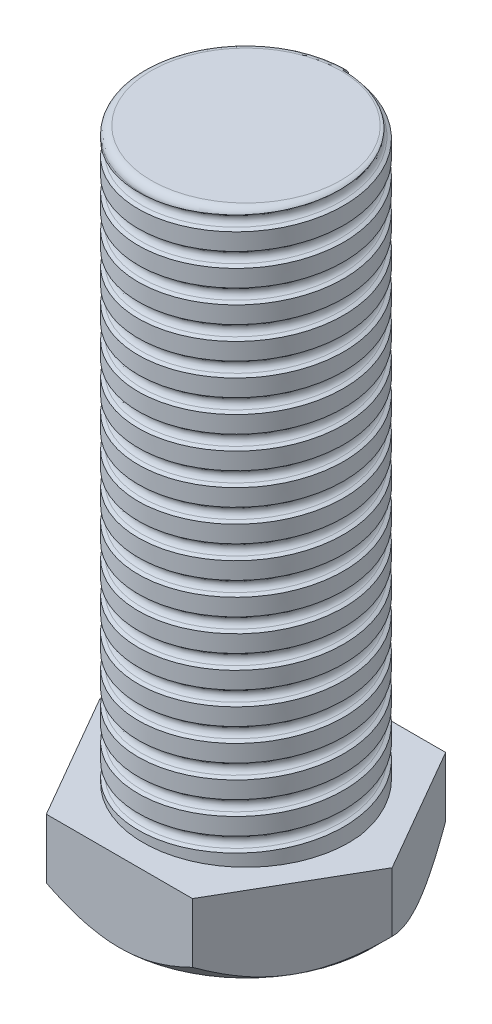
SolidWorks part; units mm, degrees
ref_plane "Front Plane" through (0, 0, 0) normal (0, 0, 1) x (1, 0, 0)
ref_plane "Top Plane" through (0, 0, 0) normal (0, 1, 0) x (1, 0, 0)
ref_plane "Right Plane" through (0, 0, 0) normal (1, 0, 0) x (0, 0, -1)
sketch "Sketch1" plane through (0, 0, 0) normal (0, 1, 0) x (1, 0, 0)
  line L1 (4.6188, -8) -> (9.2376, 0)
  line L2 (9.2376, 0) -> (4.6188, 8)
  line L3 (4.6188, 8) -> (-4.6188, 8)
  line L4 (-4.6188, 8) -> (-9.2376, 0)
  line L5 (-9.2376, 0) -> (-4.6188, -8)
  line L6 (-4.6188, -8) -> (4.6188, -8)
  circle A0 centre (0, 0) radius 8 construction
  dimension "D1" = 16
extrude "Boss-Extrude1" add sketch "Sketch1" along normal blind 5
sketch "Sketch2" plane through (0, 5, 0) normal (0, 1, 0) x (1, 0, 0)
  circle A0 centre (0, 0) radius 6.5
  dimension "D1" = 13
extrude "Boss-Extrude2" add sketch "Sketch2" along normal blind 36
sketch "Sketch3" plane through (0, 0, 0) normal (0, -1, 0) x (1, 0, 0)
  circle A0 centre (0, 0) radius 8
extrude "Cut-Extrude1" cut sketch "Sketch3" against normal blind 75 draft 45 flip side to cut
fillet "Fillet1" radius 0.5 1 edges at (0, 41, 6.5)
sketch "Sketch6" plane through (0, 41, 0) normal (0, 1, 0) x (1, 0, 0)
  circle A0 centre (0, 0) radius 6.5
  dimension "D1" = 13
curve "Helix/Spiral1" pitch 2 height 36 turns 18
sketch "Sketch7" plane through (0, 0, 0) normal (1, 0, 0) x (0, 0, -1)
  line L1 (6.9, 41.6928) -> (6.3, 41.3464)
  line L2 (6.3, 40.6536) -> (6.9, 40.3072)
  line L3 (6.9, 40.3072) -> (6.9, 41.6928)
  circle A0 centre (6.5, 41) radius 0.4 construction
  arc A1 (6.3, 40.6536) -> (6.3, 41.3464) centre (6.4889, 41) cw
  dimension "D1" = 0.8
sweep "Cut-Sweep1" cut profiles "Sketch7" path "Helix/Spiral1"
